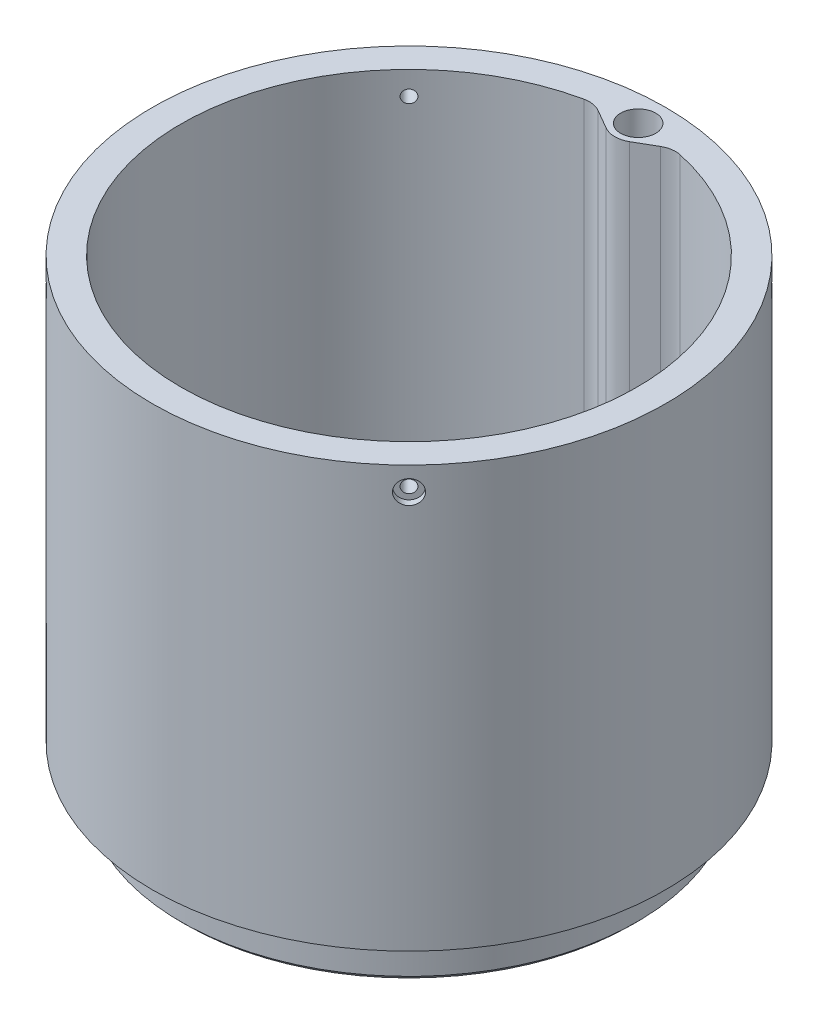
SolidWorks part; units mm, degrees
ref_plane "Piano frontale" through (0, 0, 0) normal (0, 0, 1) x (1, 0, 0)
ref_plane "Piano superiore" through (0, 0, 0) normal (0, 1, 0) x (1, 0, 0)
ref_plane "Piano destro" through (0, 0, 0) normal (1, 0, 0) x (0, 0, -1)
sketch "Schizzo1" plane through (0, 0, 0) normal (0, 1, 0) x (1, 0, 0)
  line L0 (0, 0) -> (0, 98) construction
  line L1 (-16.6526, 96.0674) -> (-5, 89.3397)
  line L2 (5, 89.3397) -> (16.6526, 96.0674)
  line L3 (-5, 89.3397) -> (0, 86.453) construction
  line L4 (0, 86.453) -> (5, 89.3397) construction
  line L5 (-21.68, 95.0591) -> (-25, 85.9375)
  line L6 (25, 85.9375) -> (21.68, 95.0591)
  line L7 (-25, 85.9375) -> (25, 85.9375) construction
  arc A0 (-16.6526, 96.0674) -> (16.6526, 96.0674) centre (0, 0) ccw
  circle A1 centre (0, 0) radius 109.75
  arc A2 (-5, 89.3397) -> (5, 89.3397) centre (0, 98) ccw
  circle A3 centre (0, 98) radius 7.5
  arc A4 (-25, 85.9375) -> (25, 85.9375) centre (0, 0) ccw
  point P5 (0, 85.9375)
  point P15 (-25, 86.453)
  point P16 (-19.694, 95.4903)
  point P17 (-29.0638, 84.6496)
  point P18 (-29.1049, 93.0546)
  dimension "D1" = 195
  dimension "D2" = 219.5
  dimension "D3" = 20
  dimension "D6" = 15
  dimension "D7" = 8
  dimension "D4" = 98
  dimension "D5" = 60
  dimension "D8" = 70
  dimension "D9" = 70
  dimension "D10" = 50
extrude "Estrusione-Estrusione1" add sketch "Schizzo1" along normal blind 180 contours A1 A3 L1 A2 L2 A0 region at (-106.6458, 0, 0)
hole_wizard "Foro lamato per Bullone M5 a testa esagonale-1" positions "Schizzo3D2" profile "Schizzo4" counterbore size "M5" standard "ISO"
sketch3d "Schizzo3D2"
  line L0 (0, 0, 0) -> (0, 170, 0) construction
  line L2 (-77.605, 170, 77.605) -> (77.605, 170, -77.605) construction
  line L3 (0, 170, 0) -> (0, 170, -109.75) construction
  line L5 (77.605, 170, 77.605) -> (-77.605, 170, -77.605) construction
  circle A0 centre (0, 170, 0) radius 109.75 construction
  circle A2 centre (0, 180, 0) radius 109.75 construction
  point P0 (-77.605, 170, -77.605)
  point P2 (-77.605, 170, 77.605)
  point P4 (77.605, 170, -77.605)
  point P6 (77.605, 170, 77.605)
  point P15 (0, 60.25, 0)
  point P35 (0, 289.75, 0)
  dimension "D1" = 170
  dimension "D2" = 45
sketch "Schizzo4" plane through (-77.605, 170, -77.605) normal (0, 1, 0) x (-0.7071, 0, 0.7071)
  line L0 (0, 0) -> (0, 21.6223)
  line L1 (0, 21.6223) -> (2.7, 20)
  line L2 (2.7, 20) -> (2.7, 3)
  line L3 (2.7, 3) -> (5, 3)
  line L4 (5, 3) -> (5, 0)
  line L5 (5, 0) -> (0, 0)
  line L10 (0, 21.6223) -> (-2.7, 20) construction
  line L11 (0, -6.35) -> (0, 107.95) construction
  dimension "Hole Dia." = 5.4
  dimension "Hole Depth" = 20
  dimension "C'Bore Dia." = 10
  dimension "C'Bore Depth" = 3
  dimension "Drill Angle" = 118
extrude "Estrusione-Estrusione2" add sketch "Schizzo1<4>" against normal blind 20 separate body contours A4 L5 A0 L6 region at (-25.9152, 0, -91.4356)
sketch "Schizzo1<4>" plane through (0, 0, 0) normal (0, 1, 0) x (1, 0, 0) same geometry as "Schizzo1"
extrude "Estrusione-Estrusione3" add sketch "Schizzo1<5>" along normal blind 10 contours A4 L5 A0 L6 region at (-25.9152, 0, -91.4356)
sketch "Schizzo1<5>" plane through (0, 0, 0) normal (0, 1, 0) x (1, 0, 0) same geometry as "Schizzo1"
chamfer "Smusso1" distance 10 angle 45 1 edges at (0, 10, 89.5)
fillet "Raccordo1" radius 10 2 edges at (16.6526, 90, -96.0674) (-16.6526, 90, -96.0674)
chamfer "Smusso2" distance 2 angle 45 2 edges at (0, -20, 89.5) (0, -20, 97.5)
